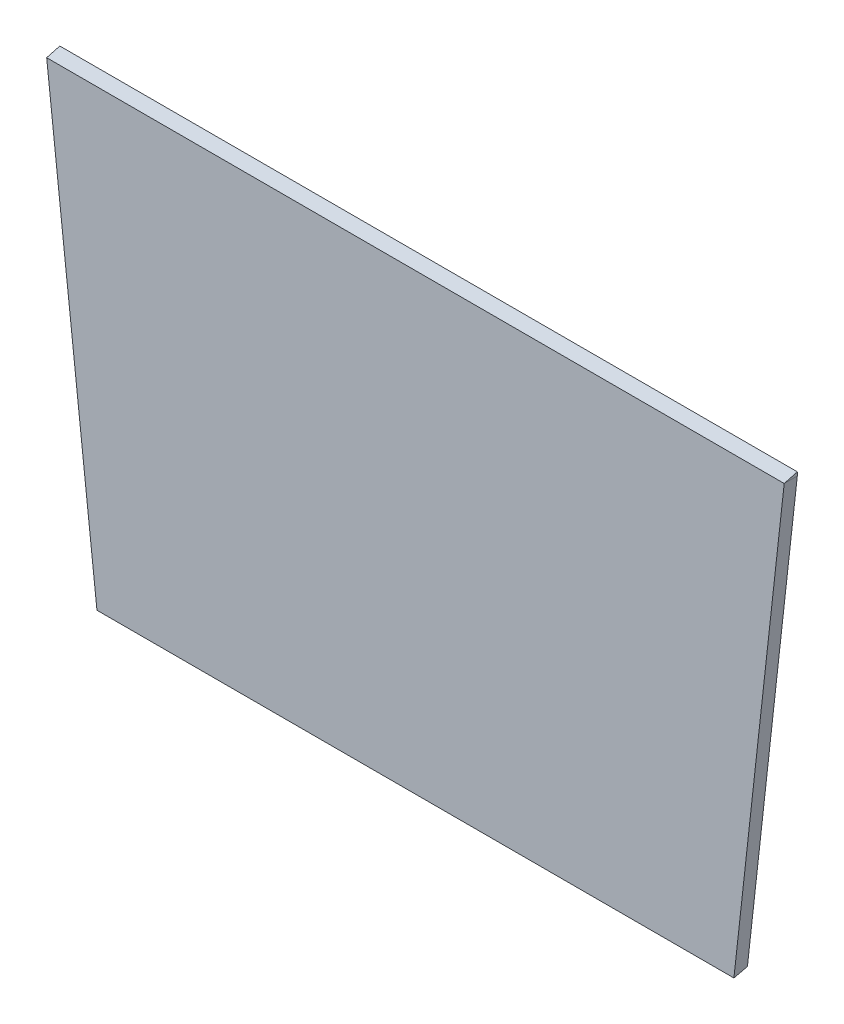
SolidWorks part; units mm, degrees
material "Verre"
ref_plane "Plan de face" through (0, 0, 0) normal (0, 0, 1) x (1, 0, 0)
ref_plane "Plan de dessus" through (0, 0, 0) normal (0, 1, 0) x (1, 0, 0)
ref_plane "Plan de droite" through (0, 0, 0) normal (1, 0, 0) x (0, 0, -1)
sketch "Esquisse1" plane through (0, 0, 0) normal (0, 0, 1) x (1, 0, 0)
  line L0 (-715.8287, 477.7037) -> (970.2413, 477.7037)
  line L1 (970.2413, 477.7037) -> (855.2513, -558.8174)
  line L2 (855.2513, -558.8174) -> (-600.8387, -558.8174)
  line L3 (-600.8387, -558.8174) -> (-715.8287, 477.7037)
  dimension "D1" = 1686.07
  dimension "D3" = 1042.88
  dimension "D4" = 1456.09
extrude "Boss.-Extru.1" add sketch "Esquisse1" along normal blind 30
sketch "Esquisse2" plane through (0, 0, 0) normal (1, 0, 0) x (0, 0, -1)
  line L0 (-30, 477.7037) -> (0, 477.7037)
  line L1 (0, 477.7037) -> (0, 485.832)
  line L2 (0, 485.832) -> (-30, 477.7037)
  dimension "D1" = 15.16
extrude "Boss.-Extru.2" add sketch "Esquisse2" along normal blind 970.2413 and the other way blind 715.8287
sketch "Esquisse3" plane through (0, 0, 0) normal (1, 0, 0) x (0, 0, -1)
  line L0 (-30, -558.8174) -> (0, -550.6891)
  line L1 (0, -558.8174) -> (0, 477.7037) construction
  line L2 (0, -550.6891) -> (0, -558.8174)
  line L3 (0, -558.8174) -> (-30, -558.8174)
  dimension "D1" = 15.16
extrude "Enlèv. mat.-Extru.1" cut sketch "Esquisse3" against normal blind 970.2413 and the other way blind 970.2413
